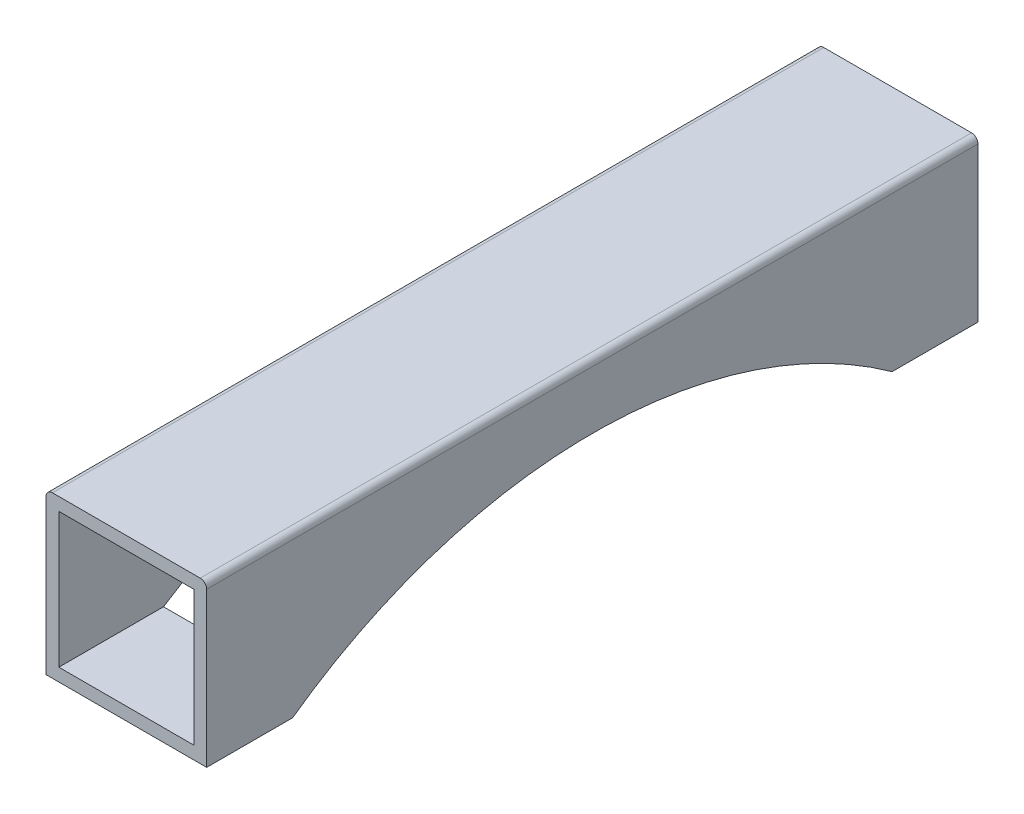
SolidWorks part; units mm, degrees
ref_plane "Спереди" through (0, 0, 0) normal (0, 0, 1) x (1, 0, 0)
ref_plane "Сверху" through (0, 0, 0) normal (0, 1, 0) x (1, 0, 0)
ref_plane "Справа" through (0, 0, 0) normal (1, 0, 0) x (0, 0, -1)
sketch "Эскиз1" plane through (0, 0, 0) normal (0, 0, 1) x (1, 0, 0)
  line L0 (-10.5, 10.5) -> (10.5, 10.5)
  line L1 (-12.5, -12.5) -> (12.5, -12.5)
  line L2 (-12.5, -12.5) -> (-12.5, 11.5)
  line L3 (-11.5, 12.5) -> (11.5, 12.5)
  line L4 (12.5, -12.5) -> (12.5, 11.5)
  line L5 (-12.5, -12.5) -> (12.5, 12.5) construction
  line L6 (-12.5, 12.5) -> (12.5, -12.5) construction
  line L7 (10.5, -10.5) -> (10.5, 10.5)
  line L8 (-10.5, -10.5) -> (10.5, -10.5)
  line L9 (-10.5, -10.5) -> (-10.5, 10.5)
  line L10 (12.5, -12.5) -> (12.5, 12.5) construction
  line L11 (-12.5, 12.5) -> (12.5, 12.5) construction
  line L12 (-12.5, -12.5) -> (-12.5, 12.5) construction
  arc A0 (12.5, 11.5) -> (11.5, 12.5) centre (11.5, 11.5) ccw
  arc A1 (-11.5, 12.5) -> (-12.5, 11.5) centre (-11.5, 11.5) ccw
  point P0 (0, 0)
  dimension "D4" = 1
  dimension "D1" = 25
  dimension "D2" = 25
  dimension "D3" = 2
extrude "Бобышка-Вытянуть1" add sketch "Эскиз1" along normal blind 60 and the other way blind 60
sketch "Эскиз2" plane through (12.5, 0, 0) normal (1, 0, 0) x (0, 0, -1)
  line L0 (-60, -12.5) -> (60, -12.5) construction
  line L1 (60, -12.5) -> (-60, -12.5) construction
  arc A0 (-46.6369, -12.5) -> (46.6369, -12.5) centre (0, -77.5) cw
  dimension "D1" = 80
  dimension "D2" = 65
extrude "Вырез-Вытянуть1" cut sketch "Эскиз2" against normal through all flip side to cut
